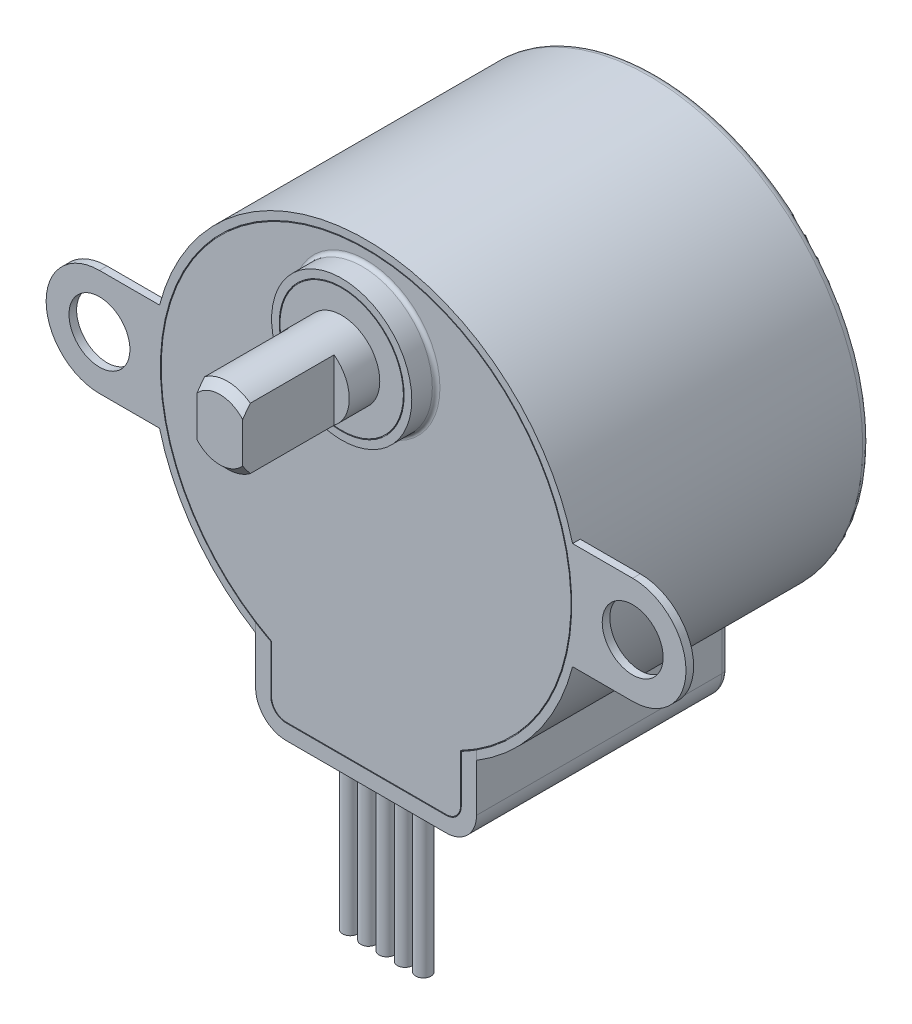
SolidWorks part; units mm, degrees
material "ASTM A36 Acero"
ref_plane "Alzado" through (0, 0, 0) normal (0, 0, 1) x (1, 0, 0)
ref_plane "Planta" through (0, 0, 0) normal (0, 1, 0) x (1, 0, 0)
ref_plane "Vista lateral" through (0, 0, 0) normal (1, 0, 0) x (0, 0, -1)
sketch "Croquis1" plane through (0, 0, 0) normal (0, 0, 1) x (1, 0, 0)
  circle A0 centre (0, 0) radius 14
  dimension "D1" = 28
extrude "Saliente-Extruir1" add sketch "Croquis1" against normal blind 19.1
sketch "Croquis2" plane through (0, 0, 0) normal (0, 0, 1) x (1, 0, 0)
  line L0 (-13.5554, 3.5) -> (-17.5, 3.5)
  line L1 (-17.5, -3.5) -> (-13.5554, -3.5)
  line L2 (0, 0) -> (0, 3.9446) construction
  circle A0 centre (-17.5, 0) radius 2
  arc A1 (-17.5, 3.5) -> (-17.5, -3.5) centre (-17.5, 0) ccw
  arc A2 (-13.5554, 3.5) -> (-13.5554, -3.5) centre (0, 0) ccw
  circle A3 centre (0, 0) radius 14 construction
  dimension "D1" = 35
  dimension "D2" = 3.5
  dimension "D3" = 4
extrude "Saliente-Extruir2" add sketch "Croquis2" against normal blind 0.5
mirror "Simetría1" about plane through (0, 0, 0) normal (1, 0, 0) of "Saliente-Extruir2"
sketch "Croquis3" plane through (0, 0, 0) normal (0, 0, 1) x (1, 0, 0)
  circle A0 centre (0, 0) radius 13.5
  arc A1 (13.5554, 3.5) -> (-13.5554, 3.5) centre (0, 0) ccw construction
  dimension "D1" = 0.5
split line "Línea de partición1"
sketch "Croquis4" plane through (0, 0, 0) normal (0, 0, 1) x (1, 0, 0)
  line L0 (0, -11.388) -> (0, 0) construction
  line L1 (-7.25, -11.388) -> (7.25, -11.388) construction
  line L2 (-7.25, -11.388) -> (-7.25, -18.3526)
  line L3 (-7.25, -18.3526) -> (7.25, -18.3526)
  line L4 (7.25, -11.388) -> (7.25, -18.3526)
  circle A0 centre (0, 0) radius 13.5 construction
  arc A1 (-7.25, -11.388) -> (7.25, -11.388) centre (0, 0) ccw
  dimension "D1" = 14.5
extrude "Cortar-Extruir1" cut sketch "Croquis4" against normal blind 16.6
sketch "Croquis5" plane through (0, 0, 0) normal (0, 0, 1) x (1, 0, 0)
  line L0 (-7.25, -11.388) -> (-7.25, -17.1)
  line L1 (-7.25, -17.1) -> (7.25, -17.1)
  line L2 (7.25, -17.1) -> (7.25, -11.388)
  arc A0 (-7.25, -11.388) -> (7.25, -11.388) centre (0, 0) ccw
  arc A1 (7.25, -11.388) -> (-7.25, -11.388) centre (0, 0) ccw construction
  arc A2 (17.5, -3.5) -> (17.5, 3.5) centre (17.5, 0) ccw construction
  dimension "D1" = 17.1
extrude "Saliente-Extruir3" add sketch "Croquis5" against normal up to surface (16.6 mm away) separate body up to face at (0, -12.7161, -16.6)
fillet "Redondeo1" radius 2 2 edges at (7.25, -17.1, -8.3) (-7.25, -17.1, -8.3)
sketch "Croquis6" plane through (0, 0, 0) normal (0, 0, 1) x (1, 0, 0)
  line L0 (-6.25, -11.388) -> (-6.25, -15.1)
  line L1 (-5.25, -16.1) -> (5.25, -16.1)
  line L2 (6.25, -15.1) -> (6.25, -11.388)
  line L3 (-5.25, -17.1) -> (5.25, -17.1)
  line L4 (7.25, -15.1) -> (7.25, -11.388)
  line L5 (-7.25, -11.388) -> (-7.25, -15.1)
  line L6 (-5.25, -17.1) -> (5.25, -17.1)
  line L7 (7.25, -15.1) -> (7.25, -11.388)
  line L8 (-7.25, -11.388) -> (-7.25, -15.1)
  line L9 (-6.25, -11.388) -> (6.25, -11.388)
  arc A0 (-6.25, -15.1) -> (-5.25, -16.1) centre (-5.25, -15.1) ccw
  arc A1 (5.25, -16.1) -> (6.25, -15.1) centre (5.25, -15.1) ccw
  arc A3 (5.25, -17.1) -> (7.25, -15.1) centre (5.25, -15.1) ccw
  arc A4 (-7.25, -11.388) -> (7.25, -11.388) centre (0, 0) ccw
  arc A5 (-7.25, -15.1) -> (-5.25, -17.1) centre (-5.25, -15.1) ccw
  arc A6 (5.25, -17.1) -> (7.25, -15.1) centre (5.25, -15.1) ccw
  arc A7 (-7.25, -11.388) -> (7.25, -11.388) centre (0, 0) ccw construction
  arc A8 (-7.25, -15.1) -> (-5.25, -17.1) centre (-5.25, -15.1) ccw
  arc M10 (7.25, -11.388) -> (-7.25, -11.388) centre (0, 0) cw
  dimension "D1" = 0
  dimension "D2" = 1
extrude "Cortar-Extruir2" cut sketch "Croquis6" against normal blind 1 contours L1 A1 L2 L0 A0 M10 region at (0, -14.5021, 0)
extrude "Saliente-Extruir4" add sketch "Croquis6<3>" against normal blind 0.5 contours L1 A1 L2 L0 A0 M10 region at (0, -14.5021, 0)
sketch "Croquis6<3>" plane through (0, 0, 0) normal (0, 0, 1) x (1, 0, 0) same geometry as "Croquis6"
fillet "Redondeo2" radius 0.5 1 edges at (14, 0, -19.1)
sketch "Croquis7" plane through (0, 0, 0) normal (0, 0, 1) x (1, 0, 0)
  circle A0 centre (0, 8) radius 4.6
  dimension "D1" = 9.2
  dimension "D2" = 8
extrude "Saliente-Extruir5" add sketch "Croquis7" along normal blind 1.6
sketch "Croquis8" plane through (0, 0, 1.6) normal (0, 0, 1) x (1, 0, 0)
  circle A0 centre (0, 8) radius 2.5
  dimension "D1" = 5
extrude "Saliente-Extruir6" add sketch "Croquis8" along normal blind 8 separate body
sketch "Croquis9" plane through (0, 0, 9.6) normal (0, 0, 1) x (1, 0, 0)
  line L1 (-1.5, 10) -> (-2.5, 10)
  line L2 (-1.5, 10) -> (-1.5, 6)
  line L3 (-1.5, 6) -> (-2.5, 6)
  line L4 (-2.5, 10) -> (-2.5, 6)
  line L5 (1.5, 10) -> (2.5, 10)
  line L6 (1.5, 10) -> (1.5, 6)
  line L7 (1.5, 6) -> (2.5, 6)
  line L8 (2.5, 10) -> (2.5, 6)
  circle A0 centre (0, 8) radius 2.5 construction
  dimension "D1" = 3
extrude "Cortar-Extruir3" cut sketch "Croquis9" against normal blind 6
fillet "Redondeo3" radius 0.5 5 edges at (7.25, -13.244, -16.6) (6.6642, -16.5142, -16.6) (0, -17.1, -16.6) (-6.6642, -16.5142, -16.6) (-7.25, -13.244, -16.6)
fillet "Redondeo4" radius 0.25 1 edges at (4.6, 8, 0)
sketch "Croquis10" plane through (0, 0, 1.6) normal (0, 0, 1) x (1, 0, 0)
  circle A0 centre (0, 8) radius 4.1
  circle A1 centre (0, 8) radius 4.6 construction
  dimension "D1" = 0.5
split line "Línea de partición2"
sketch "Croquis11" plane through (0, 0, 0) normal (0, 0, 1) x (1, 0, 0)
  line L9 (-6.2, -11.9358) -> (-6.2, -15.1)
  line L10 (-5.25, -16.05) -> (5.25, -16.05)
  line L11 (6.2, -15.1) -> (6.2, -11.9358)
  line L12 (-6.2, -11.9358) -> (-6.2, -15.1)
  line L13 (-5.25, -16.05) -> (5.25, -16.05)
  line L14 (6.2, -15.1) -> (6.2, -11.9358)
  arc A15 (6.2, -11.9358) -> (7.2231, -11.3459) centre (0, 0) ccw
  arc A16 (7.2231, -11.3459) -> (-7.2231, -11.3459) centre (0, 0) ccw
  arc A17 (-7.2231, -11.3459) -> (-6.2, -11.9358) centre (0, 0) ccw
  arc A18 (-6.2, -15.1) -> (-5.25, -16.05) centre (-5.25, -15.1) ccw
  arc A19 (5.25, -16.05) -> (6.2, -15.1) centre (5.25, -15.1) ccw
  arc A20 (6.2, -11.9358) -> (7.2231, -11.3459) centre (0, 0) ccw
  arc A21 (7.2231, -11.3459) -> (-7.2231, -11.3459) centre (0, 0) ccw
  arc A22 (-7.2231, -11.3459) -> (-6.2, -11.9358) centre (0, 0) ccw
  arc A23 (-6.2, -15.1) -> (-5.25, -16.05) centre (-5.25, -15.1) ccw
  arc A24 (5.25, -16.05) -> (6.2, -15.1) centre (5.25, -15.1) ccw
  arc M10 (6.25, -11.9661) -> (7.25, -11.388) centre (0, 0) ccw
  arc M11 (7.25, -11.388) -> (-7.25, -11.388) centre (0, 0) ccw
  arc M12 (-7.25, -11.388) -> (-6.25, -11.9661) centre (0, 0) ccw
  line M13 (-6.25, -11.9661) -> (-6.25, -15.1)
  arc M14 (-6.25, -15.1) -> (-5.25, -16.1) centre (-5.25, -15.1) ccw
  line M15 (-5.25, -16.1) -> (5.25, -16.1)
  arc M16 (5.25, -16.1) -> (6.25, -15.1) centre (5.25, -15.1) ccw
  line M17 (6.25, -15.1) -> (6.25, -11.9661)
  dimension "D1" = 0.05
extrude "Cortar-Extruir4" cut sketch "Croquis11" against normal blind 0.1 contours A24 L13 A23 L12 A22 A21 A20 L14 M17 M10 M11 M12 M13 M14 M15 M16 region at (6.2099, -13.533, 0)
sketch "Croquis12" plane through (0, 0, 1.6) normal (0, 0, 1) x (1, 0, 0)
  circle A3 centre (0, 8) radius 4.05
  circle A4 centre (0, 8) radius 4.05
  circle M2 centre (0, 8) radius 4.1
  dimension "D1" = 0.05
extrude "Cortar-Extruir5" cut sketch "Croquis12" against normal blind 0.1 contours A4 M2 region at (-4.0884, 8, 1.6)
chamfer "Chaflán1" distance 0.5 angle 45 2 edges at (0, 5.5, 9.6) (0, 10.5, 9.6)
sketch "Esquisse1" plane through (0, -17.1, 0) normal (0, -1, 0) x (1, 0, 0)
  line L0 (0, 0) -> (0, -1.359) construction
  line L1 (0, -1.359) -> (1.2, -1.359) construction
  line L2 (1.2, -1.359) -> (2.4, -1.359) construction
  circle A0 centre (0, -1.359) radius 0.5
  circle A1 centre (1.2, -1.359) radius 0.5
  circle A2 centre (2.4, -1.359) radius 0.5
  circle A3 centre (-2.4, -1.359) radius 0.5
  circle A4 centre (-1.2, -1.359) radius 0.5
  point P8 (0, -1.359)
  dimension "D1" = 1
  dimension "D2" = 1.2
extrude "Boss.-Extru.1" add sketch "Esquisse1" along normal blind 10
